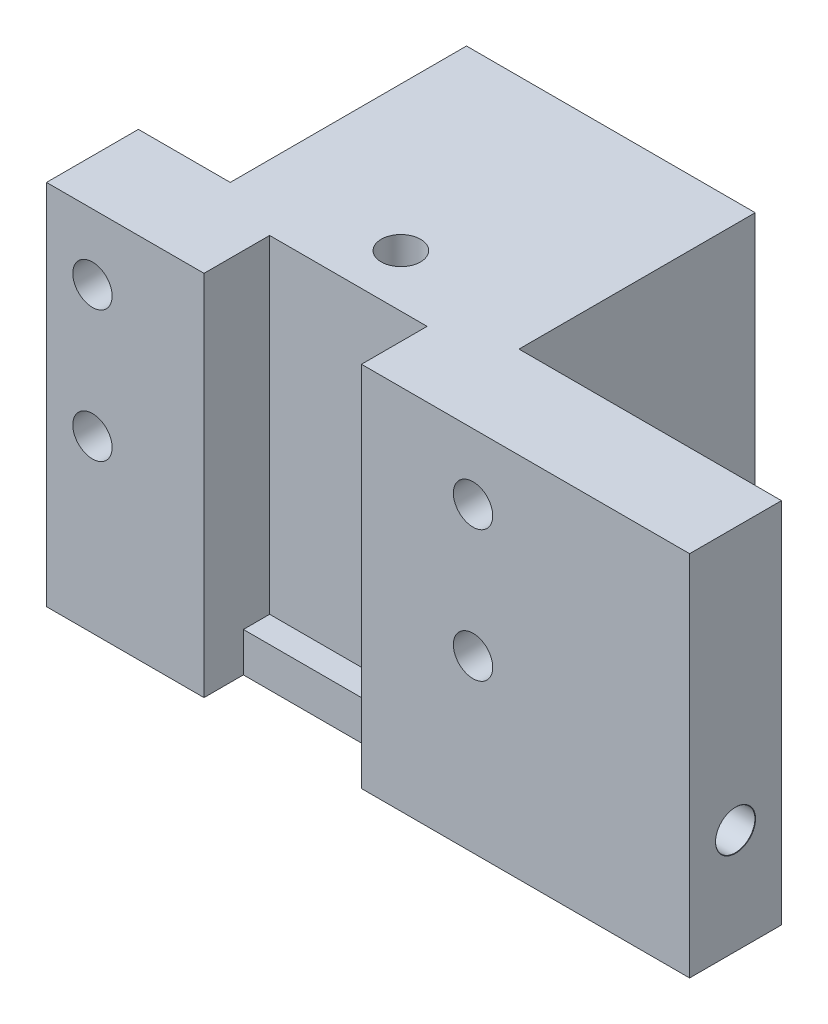
SolidWorks part; units mm, degrees
ref_plane "Front Plane" through (0, 0, 0) normal (0, 0, 1) x (1, 0, 0)
ref_plane "Top Plane" through (0, 0, 0) normal (0, 1, 0) x (1, 0, 0)
ref_plane "Right Plane" through (0, 0, 0) normal (1, 0, 0) x (0, 0, -1)
sketch "Sketch1" plane through (0, 0, 0) normal (0, 1, 0) x (1, 0, 0)
  line L1 (-10.5256, 12.3096) -> (38.4744, 12.3096)
  line L2 (-10.5256, 12.3096) -> (-10.5256, -12.6904)
  line L3 (-10.5256, -12.6904) -> (38.4744, -12.6904)
  line L4 (38.4744, 12.3096) -> (38.4744, -12.6904)
  dimension "D1" = 25
  dimension "D2" = 49
extrude "Boss-Extrude1" add sketch "Sketch1" along normal blind 28
sketch "Sketch2" plane through (0, 28, 0) normal (0, 1, 0) x (1, 0, 0)
  line L0 (-10.5256, -12.6904) -> (38.4744, -12.6904) construction
  line L1 (1.4744, -12.6904) -> (13.4744, -12.6904)
  line L2 (1.4744, -12.6904) -> (1.4744, -7.6904)
  line L3 (1.4744, -7.6904) -> (13.4744, -7.6904)
  line L4 (13.4744, -12.6904) -> (13.4744, -7.6904)
  line L5 (-10.5256, 12.3096) -> (-10.5256, -12.6904) construction
  dimension "D1" = 12
  dimension "D2" = 12
  dimension "D3" = 5
extrude "Cut-Extrude1" cut sketch "Sketch2" against normal blind 25
hole_wizard "Ø3.0mm Dowel Hole1" positions "Sketch3" profile "Sketch4" hole size "Ø3.0" standard "ANSI Metric"
sketch "Sketch3" plane through (0, 0, -12.3096) normal (0, 0, -1) x (-1, 0, 0)
  line L0 (-38.4744, 28) -> (-38.4744, 0) construction
  line L3 (-38.4744, 0) -> (10.5256, 0) construction
  point P0 (-7.4744, 16)
  dimension "D1" = 31
  dimension "D2" = 16
sketch "Sketch4" plane through (7.4744, 16, -12.3096) normal (1, 0, 0) x (0, 1, 0)
  line L0 (0, 0) -> (0, 12)
  line L1 (0, 12) -> (1.5, 11.0987)
  line L2 (1.5, 11.0987) -> (1.5, 0.025)
  line L3 (1.5, 0.025) -> (1.525, 0)
  line L5 (1.525, 0) -> (0, 0)
  line L6 (-1.5, 0.025) -> (-1.525, 0) construction
  line L10 (0, 12) -> (-1.5, 11.0987) construction
  line L11 (0, -6.35) -> (0, 107.95) construction
  dimension "Hole Dia." = 3
  dimension "Hole Depth" = 12
  dimension "Near C'Sink Dia." = 3.05
  dimension "Near C'Sink Angle" = 90
  dimension "Drill Angle" = 118
hole_wizard "Ø3.0mm Dowel Hole2" positions "Sketch7" profile "Sketch8" hole size "Ø3.0" standard "ANSI Metric" end condition up to next
sketch "Sketch7" plane through (38.4744, 0, 0) normal (1, 0, 0) x (0, 0, -1)
  line L0 (-12.6904, 0) -> (12.3096, 0) construction
  line L1 (12.3096, 28) -> (12.3096, 0) construction
  point P0 (-9.1904, 8)
  dimension "D1" = 8
  dimension "D2" = 21.5
sketch "Sketch8" plane through (38.4744, 8, 9.1904) normal (0, 1, 0) x (0, 0, -1)
  line L0 (0, 0) -> (0, 25)
  line L1 (0, 25) -> (1.5, 25)
  line L2 (1.5, 25) -> (1.5, 0.025)
  line L3 (1.5, 0.025) -> (1.525, 0)
  line L5 (1.525, 0) -> (0, 0)
  line L6 (-1.5, 0.025) -> (-1.525, 0) construction
  line L11 (0, -6.35) -> (0, 107.95) construction
  dimension "Thru Hole Dia." = 3
  dimension "Thru Hole Depth" = 25
  dimension "Near C'Sink Dia." = 3.05
  dimension "Near C'Sink Angle" = 90
hole_wizard "Ø3.0mm Dowel Hole3" positions "Sketch9" profile "Sketch10" hole size "Ø3.0" standard "ANSI Metric" end condition through all
sketch "Sketch9" plane through (0, 0, 0) normal (0, -1, 0) x (-1, 0, 0)
  line L1 (-38.4744, 12.3096) -> (10.5256, 12.3096) construction
  line L3 (-38.4744, -12.6904) -> (-38.4744, 12.3096) construction
  point P0 (-7.4744, -3.6904)
  dimension "D1" = 31
  dimension "D2" = 16
sketch "Sketch10" plane through (7.4744, 0, 3.6904) normal (1, 0, 0) x (0, 0, -1)
  line L0 (0, 0) -> (0, 28)
  line L1 (0, 28) -> (1.5, 28)
  line L2 (1.5, 28) -> (1.5, 0.025)
  line L3 (1.5, 0.025) -> (1.525, 0)
  line L5 (1.525, 0) -> (0, 0)
  line L6 (-1.5, 0.025) -> (-1.525, 0) construction
  line L11 (0, -6.35) -> (0, 107.95) construction
  dimension "Thru Hole Dia." = 3
  dimension "Thru Hole Depth" = 28
  dimension "Near C'Sink Dia." = 3.05
  dimension "Near C'Sink Angle" = 90
sketch "Sketch13" plane through (0, 0, 12.6904) normal (0, 0, 1) x (1, 0, 0)
  line L0 (-10.5256, 28) -> (1.4744, 28) construction
  line L1 (13.4744, 28) -> (38.4744, 28) construction
  line L6 (-10.5256, 28) -> (-10.5256, 0) construction
  line L7 (13.4744, 3) -> (13.4739, 8) construction
  line L8 (13.4744, 3) -> (13.4744, 28) construction
  circle A0 centre (-7.0256, 23) radius 1.5
  circle A3 centre (-7.0256, 13) radius 1.5
  circle A4 centre (21.9724, 23) radius 1.5
  circle A5 centre (21.9744, 13) radius 1.5
  dimension "D1" = 5
  dimension "D2" = 5
  dimension "D3" = 10
  dimension "D4" = 3.5
  dimension "D5" = 8.5
  dimension "D6" = 8.5
  dimension "D8" = 10
extrude "Cut-Extrude2" cut sketch "Sketch13" against normal blind 12
sketch "Sketch14" plane through (0, 28, 0) normal (0, 1, 0) x (1, 0, 0)
  line L0 (-10.5256, -12.6904) -> (1.4744, -12.6904) construction
  line L1 (-10.5256, 12.3096) -> (-3.5256, 12.3096)
  line L2 (-10.5256, 12.3096) -> (-10.5256, -5.6904)
  line L3 (-10.5256, -5.6904) -> (-3.5256, -5.6904)
  line L4 (-3.5256, 12.3096) -> (-3.5256, -5.6904)
  line L5 (1.4744, -7.6904) -> (1.4744, -12.6904) construction
  line L6 (13.4744, -12.6904) -> (38.4744, -12.6904) construction
  line L7 (18.4744, 12.3096) -> (38.4744, 12.3096)
  line L8 (18.4744, 12.3096) -> (18.4744, -5.6904)
  line L9 (18.4744, -5.6904) -> (38.4744, -5.6904)
  line L10 (38.4744, 12.3096) -> (38.4744, -5.6904)
  line L11 (13.4744, -12.6904) -> (13.4744, -7.6904) construction
  dimension "D1" = 7
  dimension "D2" = 5
  dimension "D3" = 7
  dimension "D4" = 5
extrude "Cut-Extrude3" cut sketch "Sketch14" against normal blind 28
sketch "Sketch15" plane through (0, 3, 0) normal (0, 1, 0) x (1, 0, 0)
  line L0 (13.4744, -12.6904) -> (13.4744, -7.6904) construction
  line L1 (1.4744, -12.6904) -> (13.4744, -12.6904)
  line L2 (1.4744, -12.6904) -> (1.4744, -9.6904)
  line L3 (1.4744, -9.6904) -> (13.4744, -9.6904)
  line L4 (13.4744, -12.6904) -> (13.4744, -9.6904)
  dimension "D1" = 3
extrude "Cut-Extrude4" cut sketch "Sketch15" against normal blind 10
